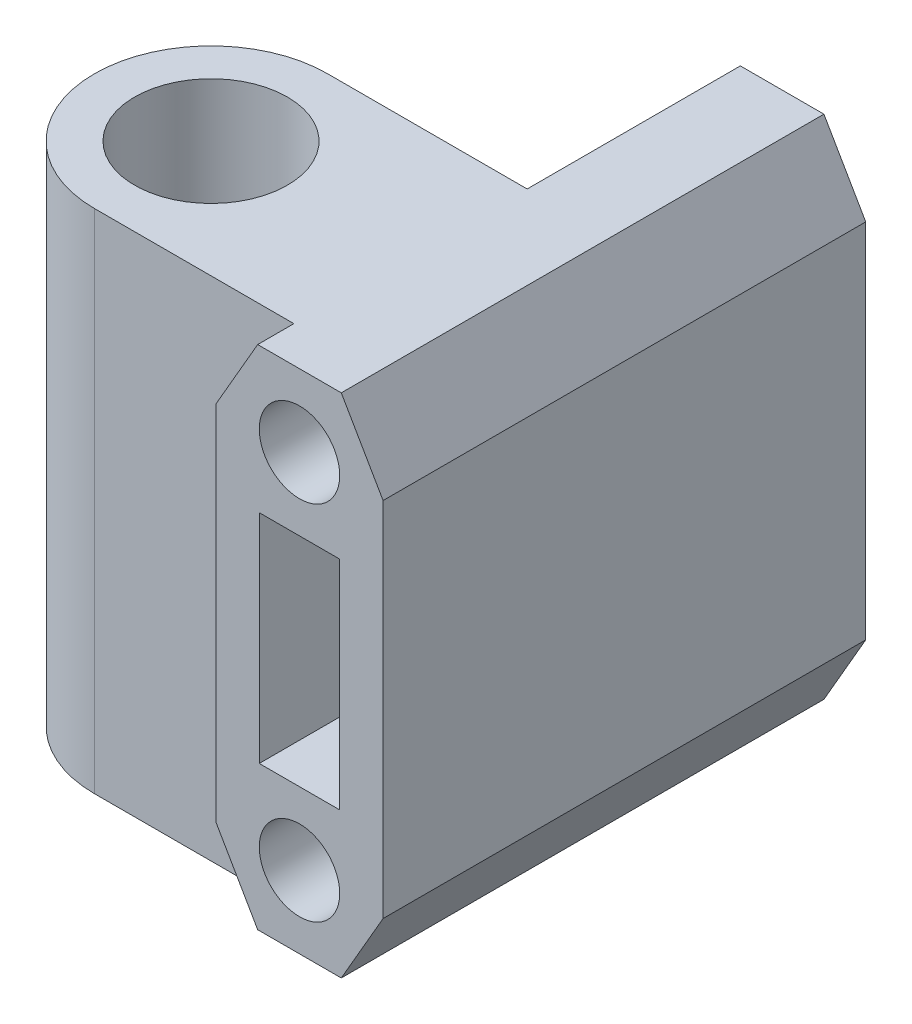
SolidWorks part; units mm, degrees
ref_plane "Front Plane" through (0, 0, 0) normal (0, 0, 1) x (1, 0, 0)
ref_plane "Top Plane" through (0, 0, 0) normal (0, 1, 0) x (1, 0, 0)
ref_plane "Right Plane" through (0, 0, 0) normal (1, 0, 0) x (0, 0, -1)
sketch "Sketch1" plane through (0, 0, 0) normal (0, 0, 1) x (1, 0, 0)
  line L0 (-10.3923, 22.5) -> (-10.3923, -22.5)
  line L1 (10.3923, 22.5) -> (5.1962, 31.5)
  line L2 (5.1962, 31.5) -> (-5.1962, 31.5)
  line L3 (-5.1962, 31.5) -> (-10.3923, 22.5)
  line L5 (-5, 13.5) -> (5, 13.5)
  line L8 (5, -13.5) -> (-5, -13.5)
  line L10 (-10.3923, -22.5) -> (-5.1962, -31.5)
  line L11 (-5.1962, -31.5) -> (5.1962, -31.5)
  line L12 (5.1962, -31.5) -> (10.3923, -22.5)
  line L13 (-5, 13.5) -> (-5, -13.5)
  line L14 (5, 13.5) -> (5, -13.5)
  line L15 (10.3923, 22.5) -> (10.3923, -22.5)
  line L17 (7.7942, 18) -> (10.3923, 22.5) [skipped]
  line L18 (-10.3923, 22.5) -> (-7.7942, 18) [skipped]
  line L19 (-7.7942, -18) -> (-10.3923, -22.5) [skipped]
  line L20 (10.3923, -22.5) -> (7.7942, -18) [skipped]
  circle A0 centre (0, 22.5) radius 5
  circle A1 centre (0, -22.5) radius 5
  circle A2 centre (0, 22.5) radius 9 construction
  circle A3 centre (0, -22.5) radius 9 construction
  dimension "D1" = 45
  dimension "D3" = 10
  dimension "D4" = 4
  dimension "D2" = 22.5
  dimension "D5" = 10
  dimension "D6" = 5
extrude "Boss-Extrude1" add sketch "Sketch1" along normal blind 60
sketch "Sketch2" plane through (0, -31.5, 0) normal (0, -1, 0) x (1, 0, 0)
  line L1 (-10.3923, 0) -> (-5.1962, 0) construction
  line L2 (-5.1962, 0) -> (5.1962, 0) construction
  line L3 (-30, 25) -> (-5.1962, 25)
  line L4 (-5.1962, 60) -> (-5.1962, 0) construction
  line L5 (-5.1962, 25) -> (-5.1962, 0)
  line L6 (-5.1962, 0) -> (-30, 0)
  circle A0 centre (-30, 12.5) radius 4.5
  arc A1 (-30, 25) -> (-30, 0) centre (-30, 12.5) ccw
  dimension "D1" = 9
  dimension "D4" = 8
  dimension "D2" = 30
  dimension "D3" = 0
  dimension "D5" = 12.5
extrude "Boss-Extrude2" add sketch "Sketch2" against normal up to surface (18 mm away) up to face at (0, -13.5, 30)
sketch "Sketch3" plane through (0, -13.5, 0) normal (0, 1, 0) x (1, 0, 0)
  line L1 (-26.2472, -6) -> (-33.7528, -6)
  line L2 (-33.7528, -6) -> (-37.5056, -12.5)
  line L3 (-37.5056, -12.5) -> (-33.7528, -19)
  line L4 (-33.7528, -19) -> (-26.2472, -19)
  line L5 (-26.2472, -19) -> (-22.4944, -12.5)
  line L6 (-22.4944, -12.5) -> (-26.2472, -6)
  circle A0 centre (-30, -12.5) radius 6.5 construction
  dimension "D1" = 13
extrude "Cut-Extrude1" cut sketch "Sketch3" against normal blind 7
sketch "Sketch4" plane through (0, -31.5, 0) normal (0, -1, 0) x (1, 0, 0)
  line L0 (-30, 12.5) -> (-30, 41) construction
  line L1 (-30, 55.5) -> (-5.1962, 55.5)
  line L2 (-5.1962, 60) -> (-5.1962, 25) construction
  line L3 (-5.1962, 55.5) -> (-5.1962, 26.5)
  line L4 (-5.1962, 26.5) -> (-30, 26.5)
  circle A0 centre (-30, 41) radius 9.5
  arc A1 (-30, 55.5) -> (-30, 26.5) centre (-30, 41) ccw
  dimension "D1" = 19
  dimension "D2" = 5
  dimension "D3" = 28.5
extrude "Boss-Extrude3" add sketch "Sketch4" against normal up to surface (63 mm away) up to face at (0, 31.5, 30)
